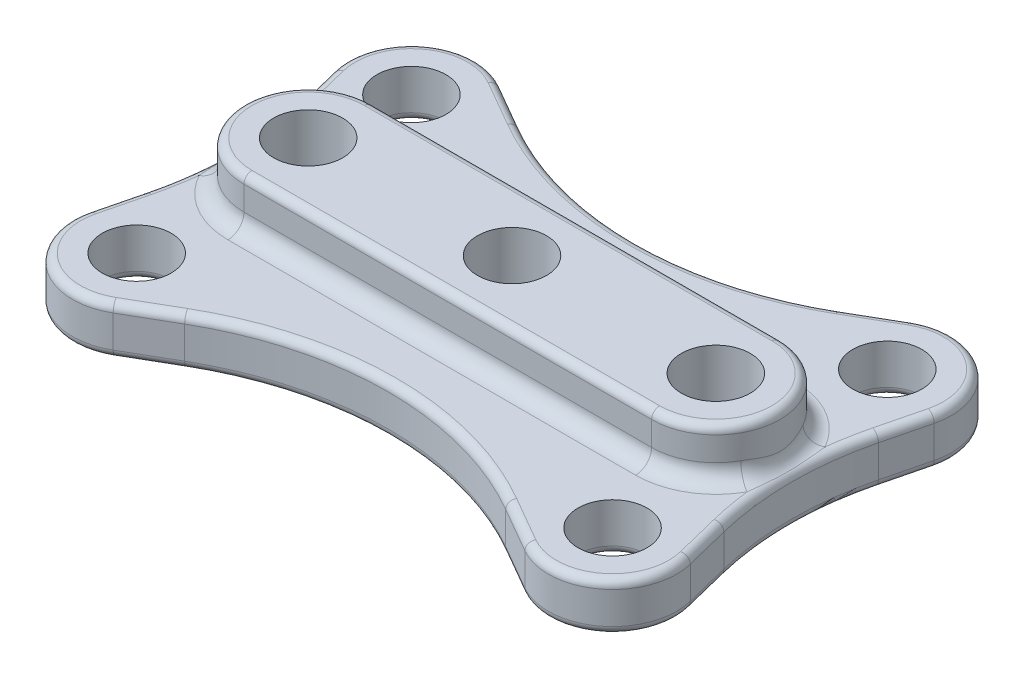
SolidWorks part; units mm, degrees
ref_plane "Front Plane" through (0, 0, 0) normal (0, 0, 1) x (1, 0, 0)
ref_plane "Top Plane" through (0, 0, 0) normal (0, 1, 0) x (1, 0, 0)
ref_plane "Right Plane" through (0, 0, 0) normal (1, 0, 0) x (0, 0, -1)
sketch "Sketch1" plane through (0, 0, 0) normal (0, 1, 0) x (1, 0, 0)
  line L0 (-12.8247, 12.0231) -> (2, 3.4641) construction
  line L1 (-18.8247, -12.559) -> (18.8247, -12.559) construction
  line L2 (-18.8247, -12.559) -> (-18.8247, 12.559) construction
  line L3 (-18.8247, 12.559) -> (18.8247, 12.559) construction
  line L4 (18.8247, -12.559) -> (18.8247, 12.559) construction
  line L5 (-18.8247, -12.559) -> (18.8247, 12.559) construction
  line L6 (-18.8247, 12.559) -> (18.8247, -12.559) construction
  line L7 (-2, 3.4641) -> (12.8247, 12.0231) construction
  line L8 (-18.7069, 7.5953) -> (-16.5822, -0.9637) construction
  line L9 (-16.5822, 0.9637) -> (-18.7069, -7.5953) construction
  line L10 (-12.8247, -12.0231) -> (2, -3.4641) construction
  line L11 (-2, -3.4641) -> (12.8247, -12.0231) construction
  line L12 (18.7069, -7.5953) -> (16.5822, 0.9637) construction
  line L13 (16.5822, -0.9637) -> (18.7069, 7.5953) construction
  line L14 (-12.8247, 12.0231) -> (0, 4.6188)
  line L15 (0, 4.6188) -> (12.8247, 12.0231)
  line L16 (18.7069, 7.5953) -> (16.8214, 0)
  line L17 (16.8214, 0) -> (18.7069, -7.5953)
  line L18 (12.8247, -12.0231) -> (0, -4.6188)
  line L19 (0, -4.6188) -> (-12.8247, -12.0231)
  line L20 (-18.7069, 7.5953) -> (-16.8214, 0)
  line L21 (-16.8214, 0) -> (-18.7069, -7.5953)
  circle A0 centre (0, 0) radius 17.1181 construction
  circle A2 centre (0, 0) radius 2.15
  circle A3 centre (14.8247, 8.559) radius 2.15
  circle A4 centre (14.8247, -8.559) radius 2.15
  circle A6 centre (-14.8247, -8.559) radius 2.15
  circle A7 centre (-14.8247, 8.559) radius 2.15
  circle A8 centre (12.7, 0) radius 2.15
  circle A9 centre (-12.7, 0) radius 2.15
  arc A10 (-12.8247, 12.0231) -> (-18.7069, 7.5953) centre (-14.8247, 8.559) ccw
  circle A11 centre (0, 0) radius 4 construction
  arc A12 (-18.7069, -7.5953) -> (-12.8247, -12.0231) centre (-14.8247, -8.559) ccw
  arc A13 (12.8247, -12.0231) -> (18.7069, -7.5953) centre (14.8247, -8.559) ccw
  arc A14 (18.7069, 7.5953) -> (12.8247, 12.0231) centre (14.8247, 8.559) ccw
  circle A15 centre (12.7, 0) radius 4 construction
  circle A16 centre (-12.7, 0) radius 4 construction
  point P43 (-16.8214, 0)
  point P44 (0, 4.6188)
  point P45 (16.8214, 0)
  point P46 (0, -4.6188)
  dimension "D1" = 34.2361
  dimension "D2" = 4
  dimension "D3" = 4.3
  dimension "D6" = 4.3
  dimension "D7" = 8
  dimension "D5" = 12.7
  dimension "D4" = 4
extrude "Boss-Extrude1" add sketch "Sketch1" along normal blind 3
fillet "Fillet1" radius 20 4 edges at (16.8214, 1.5, 0) (-16.8214, 1.5, 0) (0, 1.5, 4.6188) (0, 1.5, -4.6188)
sketch "Sketch2" plane through (0, 3, 0) normal (0, 1, 0) x (1, 0, 0)
  line L0 (-12.7, 0) -> (12.7, 0) construction
  line L1 (-12.7, 4) -> (12.7, 4)
  line L2 (-12.7, -4) -> (12.7, -4)
  line L8 (-18.7069, 7.5953) -> (-18.0175, 4.8185)
  line L9 (-18.0175, -4.8185) -> (-18.7069, -7.5953)
  line L10 (-12.8247, -12.0231) -> (-10, -10.3923)
  line L11 (10, -10.3923) -> (12.8247, -12.0231)
  line L12 (18.7069, -7.5953) -> (18.0175, -4.8185)
  line L13 (18.0175, 4.8185) -> (18.7069, 7.5953)
  line L14 (12.8247, 12.0231) -> (10, 10.3923)
  line L15 (-10, 10.3923) -> (-12.8247, 12.0231)
  line L16 (-18.7069, 7.5953) -> (-18.0175, 4.8185)
  line L17 (-18.0175, -4.8185) -> (-18.7069, -7.5953)
  line L18 (-12.8247, -12.0231) -> (-10, -10.3923)
  line L19 (10, -10.3923) -> (12.8247, -12.0231)
  line L20 (18.7069, -7.5953) -> (18.0175, -4.8185)
  line L21 (18.0175, 4.8185) -> (18.7069, 7.5953)
  line L22 (12.8247, 12.0231) -> (10, 10.3923)
  line L23 (-10, 10.3923) -> (-12.8247, 12.0231)
  arc A0 (-12.7, 4) -> (-12.7, -4) centre (-12.7, 0) ccw
  arc A1 (12.7, -4) -> (12.7, 4) centre (12.7, 0) ccw
  circle A2 centre (12.7, 0) radius 2.15 construction
  circle A3 centre (0, 0) radius 2.15 construction
  circle A4 centre (-12.7, 0) radius 2.15 construction
  circle A5 centre (12.7, 0) radius 2.15
  circle A6 centre (0, 0) radius 2.15
  circle A7 centre (-12.7, 0) radius 2.15
  arc A8 (-18.0175, -4.8185) -> (-18.0175, 4.8185) centre (-37.4284, 0) ccw
  arc A9 (-18.7069, -7.5953) -> (-12.8247, -12.0231) centre (-14.8247, -8.559) ccw
  arc A10 (10, -10.3923) -> (-10, -10.3923) centre (0, -27.7128) ccw
  arc A11 (12.8247, -12.0231) -> (18.7069, -7.5953) centre (14.8247, -8.559) ccw
  arc A12 (18.0175, 4.8185) -> (18.0175, -4.8185) centre (37.4284, 0) ccw
  arc A13 (18.7069, 7.5953) -> (12.8247, 12.0231) centre (14.8247, 8.559) ccw
  arc A14 (-10, 10.3923) -> (10, 10.3923) centre (0, 27.7128) ccw
  arc A15 (-12.8247, 12.0231) -> (-18.7069, 7.5953) centre (-14.8247, 8.559) ccw
  arc A16 (-18.0175, -4.8185) -> (-18.0175, 4.8185) centre (-37.4284, 0) ccw
  arc A17 (-18.7069, -7.5953) -> (-12.8247, -12.0231) centre (-14.8247, -8.559) ccw
  arc A18 (10, -10.3923) -> (-10, -10.3923) centre (0, -27.7128) ccw
  arc A19 (12.8247, -12.0231) -> (18.7069, -7.5953) centre (14.8247, -8.559) ccw
  arc A20 (18.0175, 4.8185) -> (18.0175, -4.8185) centre (37.4284, 0) ccw
  arc A21 (18.7069, 7.5953) -> (12.8247, 12.0231) centre (14.8247, 8.559) ccw
  arc A22 (-10, 10.3923) -> (10, 10.3923) centre (0, 27.7128) ccw
  arc A23 (-12.8247, 12.0231) -> (-18.7069, 7.5953) centre (-14.8247, 8.559) ccw
  point P12 (0, 0)
  circle M21 centre (12.7, 0) radius 2.15
  circle M38 centre (0, 0) radius 2.15
  circle M41 centre (-12.7, 0) radius 2.15
  dimension "D2" = 8
  dimension "D1" = 0
extrude "Boss-Extrude2" add sketch "Sketch2" along normal blind 3 contours L2 A1 L1 A0 A6 M41 M38 M21 region at (0, 3, -3.6566)
fillet "Fillet2" radius 0.5 43 edges at (-12.7, 0, 2.15) (-14.8247, 0, -6.409) (-14.8247, 0, 10.709) (14.8247, 0, 10.709) (14.8247, 0, -6.409) (12.7, 0, 2.15) (0, 0, 2.15) (-17.2303, 0, 11.7548) (-11.4123, 0, 11.2077) (0, 0, 7.7128) (11.4123, 0, 11.2077) (17.2303, 0, 11.7548) (18.3622, 0, 6.2069) (17.4284, 0, 0) (18.3622, 0, -6.2069) (17.2303, 0, -11.7548) (11.4123, 0, -11.2077) (0, 0, -7.7128) (-11.4123, 0, -11.2077) (-17.2303, 0, -11.7548) (-18.3622, 0, -6.2069) (-17.4284, 0, 0) (-18.3622, 0, 6.2069) (-11.4123, 3, -11.2077) (0, 3, -7.7128) (11.4123, 3, -11.2077) (17.2303, 3, -11.7548) (18.3622, 3, -6.2069) (17.4284, 3, 0) (18.3622, 3, 6.2069) (17.2303, 3, 11.7548) (11.4123, 3, 11.2077) (0, 3, 7.7128) (-11.4123, 3, 11.2077) (-17.2303, 3, 11.7548) (-18.3622, 3, 6.2069) (-17.4284, 3, 0) (-18.3622, 3, -6.2069) (-17.2303, 3, -11.7548) (-16.7, 6, 0) (0, 6, -4) (16.7, 6, 0) (0, 6, 4)
fillet "Fillet3" radius 1 4 edges at (-16.7, 3, 0) (0, 3, -4) (16.7, 3, 0) (0, 3, 4)
